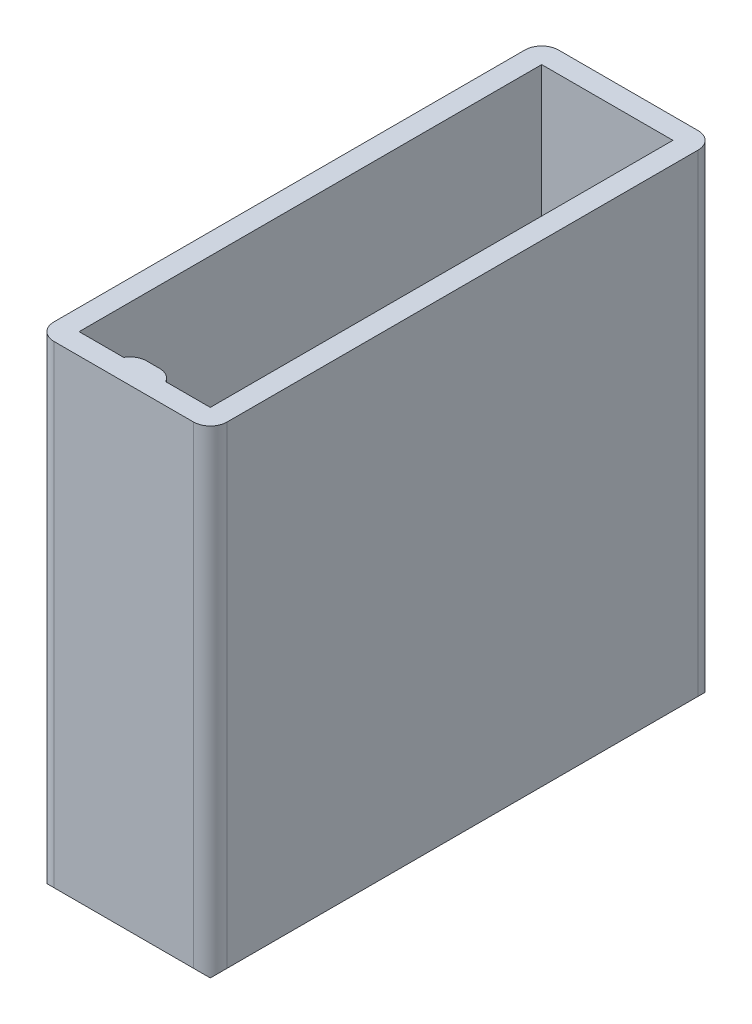
SolidWorks part; units mm, degrees
material "ABS"
ref_plane "Front Plane" through (0, 0, 0) normal (0, 0, 1) x (1, 0, 0)
ref_plane "Top Plane" through (0, 0, 0) normal (0, 1, 0) x (1, 0, 0)
ref_plane "Right Plane" through (0, 0, 0) normal (1, 0, 0) x (0, 0, -1)
sketch "Sketch1" plane through (0, 0, 0) normal (0, 0, 1) x (1, 0, 0)
  line L0 (-19.8362, 44.3895) -> (-19.8362, -31.8105)
  line L1 (-19.8362, -31.8105) -> (6.3258, -31.8105)
  line L2 (6.3258, -31.8105) -> (6.3258, 44.3895)
  line L3 (6.3258, 44.3895) -> (-19.8362, 44.3895)
  dimension "D1" = 76.2
  dimension "D2" = 26.162
extrude "Boss-Extrude1" add sketch "Sketch1" along normal mid plane 76.2
sketch "Sketch2" plane through (0, 44.3895, 0) normal (0, 1, 0) x (1, 0, 0)
  line L0 (-16.6612, 34.925) -> (-16.6612, -34.925)
  line L1 (-16.6612, -34.925) -> (3.1508, -34.925)
  line L2 (3.1508, -34.925) -> (3.1508, 34.925)
  line L3 (3.1508, 34.925) -> (-16.6612, 34.925)
  line L4 (-19.8362, -38.1) -> (-19.8362, 38.1) construction
  line L5 (6.3258, -38.1) -> (-19.8362, -38.1) construction
  line L6 (6.3258, -38.1) -> (6.3258, 38.1) construction
  line L7 (6.3258, 38.1) -> (-19.8362, 38.1) construction
  dimension "D1" = 3.175
  dimension "D2" = 3.175
  dimension "D3" = 3.175
  dimension "D4" = 3.175
extrude "Cut-Extrude1" cut sketch "Sketch2" against normal blind 73.025
chamfer "Chamfer1" distance 4.7625 angle 45 4 edges at (-19.8362, -31.8105, 0) (-6.7552, -31.8105, -38.1) (6.3258, -31.8105, 0) (-6.7552, -31.8105, 38.1)
sketch "Sketch3" plane through (0, 0, 34.925) normal (0, 0, -1) x (-1, 0, 0)
  line L0 (3.5802, 44.3895) -> (3.5802, 43.6021)
  line L1 (-6.3258, 44.3895) -> (19.8362, 44.3895) construction
  line L2 (3.5802, 43.6021) -> (9.9302, 43.6021)
  line L3 (9.9302, 43.6021) -> (9.9302, 44.3895)
  line L4 (9.9302, 44.3895) -> (3.5802, 44.3895)
  point P4 (6.7552, 44.3895)
  dimension "D1" = 0.7874
  dimension "D2" = 6.35
extrude "Boss-Extrude2" add sketch "Sketch3" along normal blind 1.27
fillet "Fillet1" radius 2.54 4 edges at (-19.8362, 8.6708, -38.1) (6.3258, 8.6708, -38.1) (6.3258, 8.6708, 38.1) (-19.8362, 8.6708, 38.1)
fillet "Fillet2" radius 2.54 2 edges at (-3.5802, 43.9958, 33.655) (-9.9302, 43.9958, 33.655)
